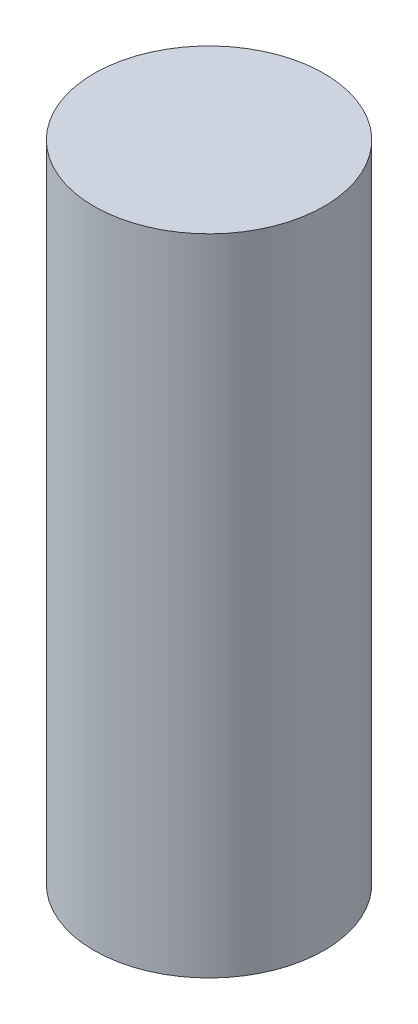
SolidWorks part; units mm, degrees
ref_plane "Front Plane" through (0, 0, 0) normal (0, 0, 1) x (1, 0, 0)
ref_plane "Top Plane" through (0, 0, 0) normal (0, 1, 0) x (1, 0, 0)
ref_plane "Right Plane" through (0, 0, 0) normal (1, 0, 0) x (0, 0, -1)
sketch "Sketch1" plane through (0, 0, 0) normal (0, 1, 0) x (1, 0, 0)
  circle A0 centre (0, 0) radius 5
  dimension "D1" = 10
extrude "Boss-Extrude1" add sketch "Sketch1" along normal blind 14 and the other way blind 14
